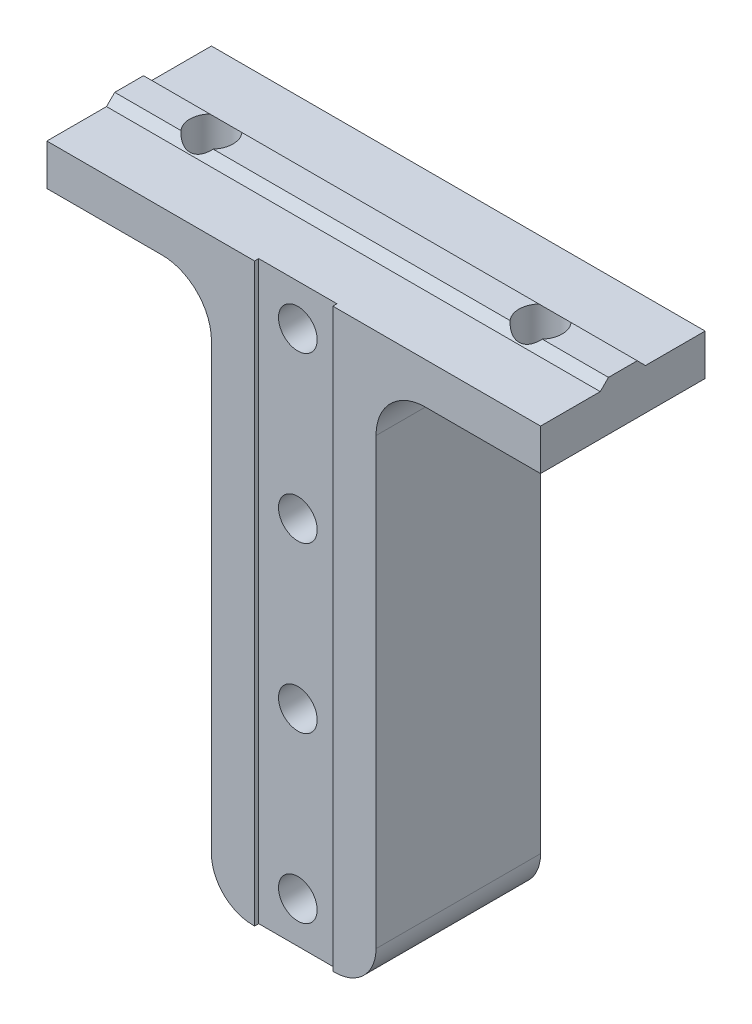
SolidWorks part; units mm, degrees
ref_plane "Front Plane" through (0, 0, 0) normal (0, 0, 1) x (1, 0, 0)
ref_plane "Top Plane" through (0, 0, 0) normal (0, 1, 0) x (1, 0, 0)
ref_plane "Right Plane" through (0, 0, 0) normal (1, 0, 0) x (0, 0, -1)
sketch "Sketch2" plane through (0, 0, 0) normal (0, 0, 1) x (1, 0, 0)
  line L1 (-10.4688, 43.5938) -> (9.5312, 43.5938)
  line L2 (-10.4688, 43.5938) -> (-10.4687, -26.4062)
  line L3 (-10.4687, -26.4062) -> (9.5313, -26.4062)
  line L4 (9.5312, 43.5938) -> (9.5313, -26.4062)
  dimension "D1" = 20
  dimension "D2" = 70
extrude "Boss-Extrude1" add sketch "Sketch2" along normal blind 20
sketch "Sketch3" plane through (0, 0, 20) normal (0, 0, 1) x (1, 0, 0)
  line L0 (9.5312, 43.5938) -> (-10.4688, 43.5938) construction
  line L1 (-5.2188, 43.5938) -> (4.2812, 43.5938)
  line L2 (-5.2188, 43.5938) -> (-5.2187, -26.4062)
  line L3 (-5.2187, -26.4062) -> (4.2813, -26.4062)
  line L4 (4.2812, 43.5938) -> (4.2813, -26.4062)
  line L5 (-10.4687, -26.4062) -> (9.5313, -26.4062) construction
  line L6 (-10.4688, 43.5938) -> (-10.4688, -26.4062) construction
  dimension "D1" = 9.5
  dimension "D2" = 5.25
extrude "Cut-Extrude1" cut sketch "Sketch3" against normal blind 0.5
sketch "Sketch4" plane through (0, 0, 19.5) normal (0, 0, 1) x (1, 0, 0)
  line L0 (-5.2187, -26.4062) -> (4.2813, -26.4062) construction
  line L1 (-10.4688, 43.5938) -> (-10.4688, -26.4062) construction
  circle A0 centre (-0.4688, 38.5938) radius 2.35
  circle A1 centre (-0.4688, 18.5938) radius 2.35
  circle A2 centre (-0.4688, -1.4062) radius 2.35
  circle A5 centre (-0.4688, 78.5938) radius 2.35
  circle A7 centre (-0.4688, -21.4062) radius 2.35
  circle A8 centre (-0.4688, 58.5938) radius 2.35
  dimension "D7" = 4.7
  dimension "D8" = 4.7
  dimension "D9" = 4.7
  dimension "D10" = 5
  dimension "D13" = 4.7
  dimension "D15" = 10
  dimension "D16" = 20
  dimension "D4" = 4.7
  dimension "D17" = 4.7
  dimension "D2" = 20
  dimension "D3" = 20
  dimension "D5" = 10
  dimension "D6" = 10
  dimension "D11" = 10
  dimension "D12" = 20
  dimension "D14" = 20
  dimension "D18" = 10
  dimension "D19" = 10
extrude "Cut-Extrude2" cut sketch "Sketch4" against normal blind 5.5
sketch "Sketch5" plane through (0, 43.5938, 0) normal (0, 1, 0) x (1, 0, 0)
  line L1 (9.5312, 0) -> (29.5312, 0)
  line L2 (9.5312, 0) -> (9.5312, -20)
  line L3 (9.5312, -20) -> (29.5312, -20)
  line L4 (29.5312, 0) -> (29.5312, -20)
  line L5 (-10.4688, 0) -> (-30.4688, 0)
  line L6 (-10.4688, 0) -> (-10.4688, -20)
  line L7 (-10.4688, -20) -> (-30.4688, -20)
  line L8 (-30.4688, 0) -> (-30.4688, -20)
  dimension "D1" = 20
  dimension "D2" = 20
extrude "Boss-Extrude2" add sketch "Sketch5" against normal blind 5
fillet "Fillet1" radius 6 1 edges at (9.5312, 38.5938, 10)
fillet "Fillet2" radius 6 1 edges at (-10.4688, 38.5938, 10)
sketch "Sketch6" plane through (0, 43.5938, 0) normal (0, 1, 0) x (1, 0, 0)
  line L0 (-30.4688, 0) -> (-30.4688, -20) construction
  line L1 (-30.4688, -7.25) -> (29.5312, -7.25)
  line L2 (-30.4688, -7.25) -> (-30.4688, -12.75)
  line L3 (-30.4688, -12.75) -> (29.5312, -12.75)
  line L4 (29.5312, -7.25) -> (29.5312, -12.75)
  line L5 (29.5312, -20) -> (29.5312, 0) construction
  line L6 (29.5312, 0) -> (-30.4688, 0) construction
  line L7 (-5.2188, -20) -> (-30.4688, -20) construction
  dimension "D1" = 7.25
  dimension "D2" = 7.25
extrude "Boss-Extrude3" add sketch "Sketch6" along normal blind 1
chamfer "Chamfer1" distance 1 angle 45 2 edges at (-0.4688, 44.5938, 7.25) (-0.4688, 44.5938, 12.75)
sketch "Sketch7" plane through (0, 38.5938, 0) normal (0, -1, 0) x (1, 0, 0)
  line L0 (-30.4688, 20) -> (-16.4688, 20) construction
  line L1 (-30.4688, 0) -> (-30.4688, 20) construction
  line L2 (29.5312, 20) -> (29.5312, 0) construction
  line L3 (15.5312, 20) -> (29.5312, 20) construction
  circle A0 centre (19.5312, 10) radius 2.625
  circle A1 centre (-20.4688, 10) radius 2.625
  dimension "D5" = 5.25
  dimension "D6" = 5.25
  dimension "D1" = 10
  dimension "D2" = 10
  dimension "D3" = 10
  dimension "D4" = 10
extrude "Cut-Extrude3" cut sketch "Sketch7" against normal through all
fillet "Fillet3" radius 5 1 edges at (-10.4687, -26.4062, 10)
fillet "Fillet4" radius 5 1 edges at (9.5313, -26.4062, 10)
